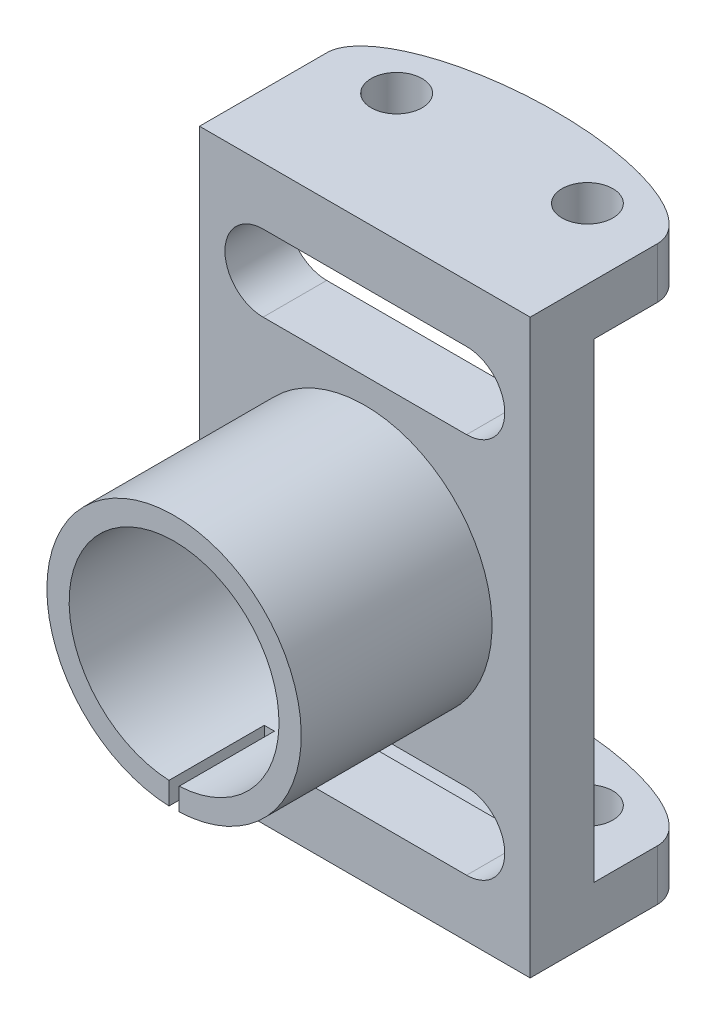
SolidWorks part; units mm, degrees
ref_plane "Front Plane" through (0, 0, 0) normal (0, 0, 1) x (1, 0, 0)
ref_plane "Top Plane" through (0, 0, 0) normal (0, 1, 0) x (1, 0, 0)
ref_plane "Right Plane" through (0, 0, 0) normal (1, 0, 0) x (0, 0, -1)
sketch "Sketch1" plane through (0, 0, 0) normal (0, 0, 1) x (1, 0, 0)
  line L0 (21, 37.5) -> (5, 37.5) construction
  line L1 (0, 0) -> (26, 0)
  line L2 (0, 0) -> (0, 45)
  line L3 (0, 45) -> (26, 45)
  line L4 (26, 0) -> (26, 45)
  line L5 (21, 34.5) -> (5, 34.5)
  line L6 (21, 40.5) -> (5, 40.5)
  line L7 (43.5373, 22.5) -> (-17.5373, 22.5) construction
  line L8 (21, 7.5) -> (5, 7.5) construction
  line L9 (21, 10.5) -> (5, 10.5)
  line L10 (21, 4.5) -> (5, 4.5)
  circle A0 centre (13, 22.5) radius 8.25
  arc A1 (21, 34.5) -> (21, 40.5) centre (21, 37.5) ccw
  arc A2 (5, 40.5) -> (5, 34.5) centre (5, 37.5) ccw
  arc A3 (21, 10.5) -> (21, 4.5) centre (21, 7.5) cw
  arc A4 (5, 4.5) -> (5, 10.5) centre (5, 7.5) cw
  point P8 (13, 0)
  point P9 (13, 37.5)
  point P10 (26, 22.5)
  point P19 (13, 22.5)
  point P22 (13, 7.5)
  dimension "D3" = 16.5
  dimension "D5" = 3
  dimension "D1" = 45
  dimension "D2" = 26
  dimension "D4" = 16
  dimension "D6" = 15
extrude "Boss-Extrude1" add sketch "Sketch1" along normal blind 5
sketch "Sketch2" plane through (0, 0, 5) normal (0, 0, 1) x (1, 0, 0)
  circle A0 centre (13, 22.5) radius 8.25 construction
  circle A1 centre (13, 22.5) radius 8.25
  circle A2 centre (13, 22.5) radius 10
  dimension "D1" = 20
extrude "Boss-Extrude2" add sketch "Sketch2" along normal blind 7.5
sketch "Sketch3" plane through (0, 0, 12.5) normal (0, 0, 1) x (1, 0, 0)
  line L0 (13.4, 14.2597) -> (13.4, 12.508)
  line L1 (12.6, 14.2597) -> (12.6, 12.508)
  line L2 (13, 22.5) -> (13, -5.7001)
  circle A0 centre (13, 22.5) radius 8.25 construction
  circle A1 centre (13, 22.5) radius 10
  arc A2 (13.4, 12.508) -> (12.6, 12.508) centre (13, 22.5) ccw
  arc A3 (13.4, 14.2597) -> (12.6, 14.2597) centre (13, 22.5) ccw
  circle A4 centre (13, 22.5) radius 10 construction
  circle M4 centre (13, 22.5) radius 10
  circle M5 centre (13, 22.5) radius 8.25
  dimension "D2" = 0.8
  dimension "D3" = 0.4
  dimension "D4" = 0.4
  dimension "D1" = 0
extrude "Boss-Extrude3" add sketch "Sketch3" along normal blind 7.5 contours L1 L0 M5 M4 region at (19.1781, 16.6145, 12.5)
sketch "Sketch4" plane through (13.4, 0, 0) normal (-1, 0, 0) x (0, 0, 1)
  line L1 (25, 15.7049) -> (25, 10.7049)
  line L2 (20, 14.2597) -> (20, 12.508) construction
  line L4 (12.5, 14.2597) -> (12.5, 12.508)
  line L5 (12.5, 12.508) -> (20, 12.508)
  line L6 (20, 12.508) -> (20, 14.2597)
  line L7 (20, 14.2597) -> (12.5, 14.2597)
  line L8 (12.5, 15.7049) -> (12.5, 10.7049)
  line L9 (12.5, 10.7049) -> (25, 10.7049)
  line L11 (25, 15.7049) -> (12.5, 15.7049)
  dimension "D2" = 5
  dimension "D1" = 0
ref_plane "Plane1" through (13, 0, 0) normal (1, 0, 0) x (0, 0, -1)
sketch "Sketch5" plane through (0, 45, 0) normal (0, 1, 0) x (1, 0, 0)
  line L0 (13, 0) -> (13, 10) construction
  line L1 (26, 0) -> (0, 0) construction
  line L2 (0, 5) -> (0, 0)
  line L3 (0, 0) -> (26, 0)
  line L4 (26, 0) -> (26, 5)
  circle A0 centre (5.5, 5) radius 2
  circle A1 centre (20.5, 5) radius 2
  ellipse E0 centre (13, 5) end of major axis (26, 5) minor radius 5 (26, 5) -> (0, 5) ccw
  dimension "D5" = 4
  dimension "D1" = 7.5
  dimension "D2" = 5
  dimension "D3" = 5
  dimension "D4" = 7.5
extrude "Boss-Extrude4" add sketch "Sketch5" against normal blind 4
extrude "Boss-Extrude5" add sketch "Sketch5<2>" along normal blind 4 from offset 45 offset against normal yes
sketch "Sketch5<2>" plane through (0, 45, 0) normal (0, 1, 0) x (1, 0, 0) same geometry as "Sketch5"
